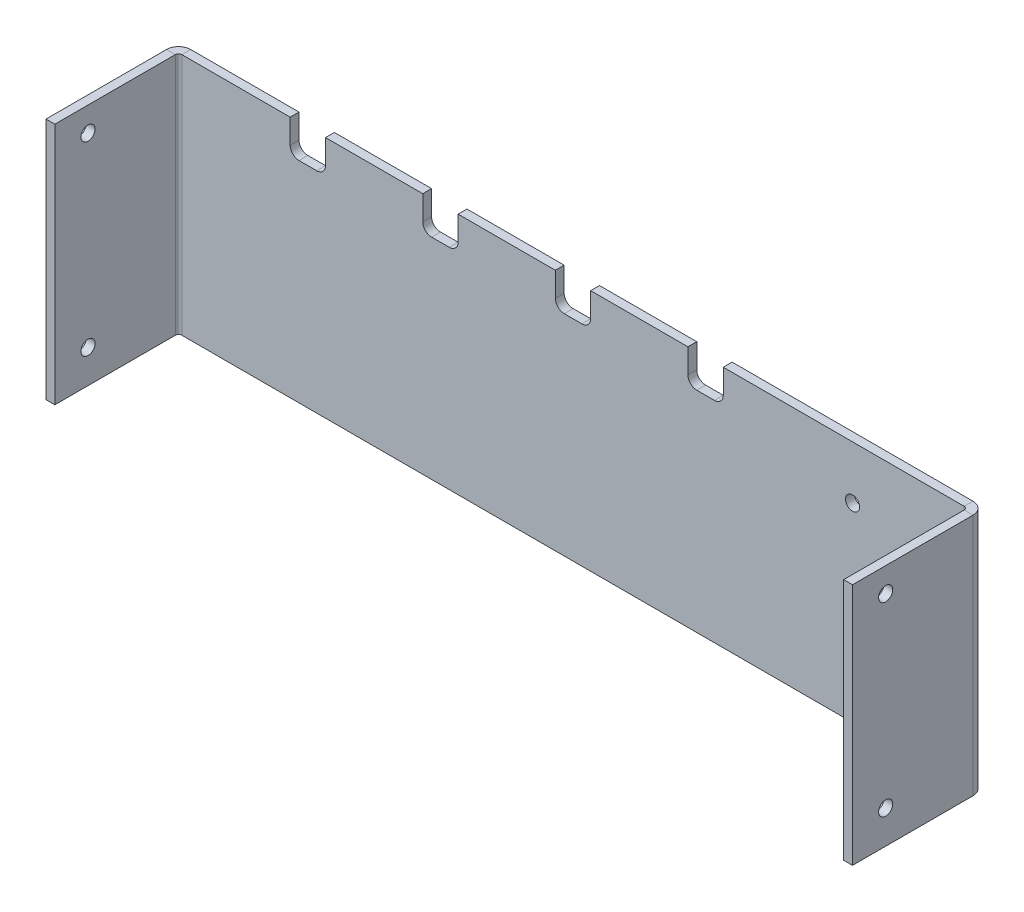
SolidWorks part; units mm, degrees
note: The reader was unsure of these and kept them because the rebuilt part matched: flange length of "Ребро-кромка1".
ref_plane "Спереди" through (0, 0, 0) normal (0, 0, 1) x (1, 0, 0)
ref_plane "Сверху" through (0, 0, 0) normal (0, 1, 0) x (1, 0, 0)
ref_plane "Справа" through (0, 0, 0) normal (1, 0, 0) x (0, 0, -1)
sketch "Эскиз1" plane through (0, 0, 0) normal (0, 0, 1) x (1, 0, 0)
  line L1 (-91.25, 27.5) -> (91.25, 27.5)
  line L2 (-91.25, 27.5) -> (-91.25, -27.5)
  line L3 (-91.25, -27.5) -> (91.25, -27.5)
  line L4 (91.25, 27.5) -> (91.25, -27.5)
  line L5 (0, -27.5) -> (0, 27.5) construction
  line L6 (-91.25, 0) -> (91.25, 0) construction
  point P0 (0, 0)
  dimension "D1" = 182.5
  dimension "D2" = 55
base flange "Базовая кромка1" sketch "Эскиз1" thickness 2 reverse thickness direction no parameters "D1"=0.7366
edge flange "Ребро-кромка1" sketch "Эскиз10" flange profiles "Эскиз10", "Эскиз11" flange angle 90 flange length 30 flange position material inside bend radius 0.7366 thickness 2 relief rectangular parameters "D6"=10, "D8"=1
sketch "Эскиз10" plane through (-91.25, 0, 0) normal (1, 0, 0) x (0, 1, 0)
  line L2 (-27.5, 0) -> (-27.5, 28)
  line L3 (-27.5, 28) -> (27.5, 28)
  line L4 (27.5, 28) -> (27.5, 0)
  line L6 (27.5, 0) -> (-27.5, 0) construction
  line L7 (27.5, 0) -> (-27.5, 0)
sketch "Эскиз11" plane through (91.25, 0, 0) normal (-1, 0, 0) x (0, -1, 0)
  line L1 (27.5, 0) -> (-27.5, 0) construction
  line L2 (-27.5, 0) -> (-27.5, 28)
  line L3 (-27.5, 28) -> (27.5, 28)
  line L4 (27.5, 28) -> (27.5, 0)
  line L5 (27.5, 0) -> (-27.5, 0)
bend "EdgeBend1" bend radius 0.7366 bend angle 90 parameters "D5"=1
bend "EdgeBend2" bend radius 0.7366 bend angle 90 parameters "D5"=2
sketch "Эскиз12" plane through (0, 0, 0) normal (0, 0, 1) x (1, 0, 0)
  line L0 (88.5134, 27.5) -> (-88.5134, 27.5) construction
  line L2 (-4, 27.5) -> (-4, 20)
  line L3 (-4, 20) -> (4, 20)
  line L4 (4, 27.5) -> (4, 20)
  line L5 (0, 20) -> (0, 27.5) construction
  line L6 (-4, 27.5) -> (4, 27.5) construction
  line L7 (-4, 27.5) -> (4, 27.5)
  line L8 (26, 20) -> (34, 20)
  line L9 (26, 27.5) -> (26, 20)
  line L10 (34, 27.5) -> (34, 20)
  line L11 (26, 27.5) -> (34, 27.5)
  line L12 (-34, 20) -> (-26, 20)
  line L13 (-34, 27.5) -> (-34, 20)
  line L14 (-26, 27.5) -> (-26, 20)
  line L15 (-34, 27.5) -> (-26, 27.5)
  line L16 (-64, 20) -> (-56, 20)
  line L17 (-64, 27.5) -> (-64, 20)
  line L18 (-56, 27.5) -> (-56, 20)
  line L19 (-64, 27.5) -> (-56, 27.5)
  point P0 (0, 27.5)
  dimension "D1" = 8
  dimension "D2" = 7.5
  dimension "D3" = 2
  dimension "D4" = 3
extrude "Вырез-Вытянуть1" cut sketch "Эскиз12" against normal blind 10 normal cut yes
fillet "Скругление1" radius 2 8 edges at (34, 20, -1) (26, 20, -1) (4, 20, -1) (-4, 20, -1) (-56, 20, -1) (-64, 20, -1) (-26, 20, -1) (-34, 20, -1)
sketch "Эскиз13" plane through (91.25, 0, 0) normal (1, 0, 0) x (0, 0, -1)
  line L0 (-28, 27.5) -> (-0.7366, 27.5) construction
  line L2 (-28, -27.5) -> (-28, 27.5) construction
  circle A0 centre (-20.5, 22) radius 1.6
  circle A1 centre (-20.5, -20) radius 1.6
  dimension "D1" = 3.2
  dimension "D2" = 7.5
  dimension "D3" = 5.5
  dimension "D4" = 2
extrude "Вырез-Вытянуть2" cut sketch "Эскиз13" against normal blind 197 contours A1 | A0 normal cut yes
sketch "Эскиз14" plane through (0, 0, -2) normal (0, 0, -1) x (-1, 0, 0)
  line L0 (-88.5134, 27.5) -> (-34, 27.5) construction
  line L1 (-91.25, -27.5) -> (-91.25, 27.5) construction
  line L2 (-63.25, 15.5) -> (-63.25, -9.5) construction
  circle A0 centre (-63.25, 15.5) radius 1.6
  circle A1 centre (-63.25, -9.5) radius 1.6
  dimension "D1" = 3.2
  dimension "D3" = 28
  dimension "D5" = 3.2
  dimension "D2" = 12
  dimension "D4" = 25
extrude "Вырез-Вытянуть3" cut sketch "Эскиз14" against normal blind 10 normal cut yes
sketch "Сгиб-Линии1" plane through (0, 0, 0) normal (0, 1, 0) x (1, 0, 0)
sketch "Граничная рамка1" plane through (0, 0, 0) normal (0, 1, 0) x (1, 0, 0)
sheet metal parameters "Листовой металл3" thickness 2 parameters "D1"=0.7366
flat pattern "Развертка3" [suppressed]
sketch "Сгиб-Линии2" plane through (0, 0, 0) normal (0, 1, 0) x (1, 0, 0)
sketch "Граничная рамка2" [suppressed] plane through (0, 0, 0) normal (0, 1, 0) x (1, 0, 0)
sheet metal parameters "Листовой металл4" thickness 2 parameters "D1"=0.7366
flat pattern "Развертка3" [suppressed]
sketch "Сгиб-Линии2" plane through (0, 0, 0) normal (0, 1, 0) x (1, 0, 0)
sketch "Граничная рамка2" [suppressed] plane through (0, 0, 0) normal (0, 1, 0) x (1, 0, 0)
bend of the flat pattern "Плоское состояние-<EdgeBend1>1"
bend of the flat pattern "Плоское состояние-<EdgeBend2>1"
sheet metal parameters "Листовой металл5" thickness 2 parameters "D1"=0.7366
flat pattern "Развертка3" [suppressed]
sketch "Сгиб-Линии2" plane through (0, 0, 0) normal (0, 1, 0) x (1, 0, 0)
sketch "Граничная рамка2" [suppressed] plane through (0, 0, 0) normal (0, 1, 0) x (1, 0, 0)
bend of the flat pattern "Плоское состояние-<EdgeBend1>1"
bend of the flat pattern "Плоское состояние-<EdgeBend2>1"
sheet metal parameters "Листовой металл6" thickness 2 parameters "D1"=0.7366
flat pattern "Развертка3" [suppressed]
sketch "Сгиб-Линии2" plane through (0, 0, 0) normal (0, 1, 0) x (1, 0, 0)
sketch "Граничная рамка2" [suppressed] plane through (0, 0, 0) normal (0, 1, 0) x (1, 0, 0)
bend of the flat pattern "Плоское состояние-<EdgeBend1>1"
bend of the flat pattern "Плоское состояние-<EdgeBend2>1"
sheet metal parameters "Листовой металл7" thickness 2 parameters "D1"=0.7366
flat pattern "Развертка3" [suppressed]
sketch "Сгиб-Линии2" plane through (0, 0, 0) normal (0, 1, 0) x (1, 0, 0)
sketch "Граничная рамка2" [suppressed] plane through (0, 0, 0) normal (0, 1, 0) x (1, 0, 0)
bend of the flat pattern "Плоское состояние-<EdgeBend1>1"
bend of the flat pattern "Плоское состояние-<EdgeBend2>1"
